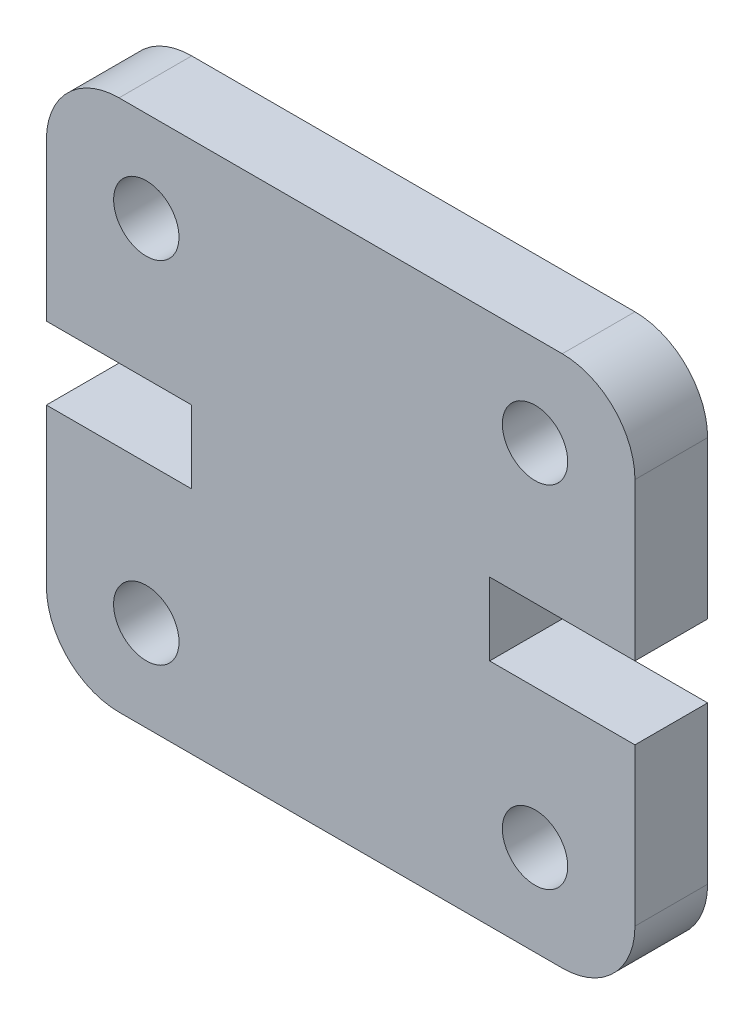
SolidWorks part; units mm, degrees
ref_plane "Front Plane" through (0, 0, 0) normal (0, 0, 1) x (1, 0, 0)
ref_plane "Top Plane" through (0, 0, 0) normal (0, 1, 0) x (1, 0, 0)
ref_plane "Right Plane" through (0, 0, 0) normal (1, 0, 0) x (0, 0, -1)
sketch "Sketch1" plane through (0, 0, 0) normal (0, 0, 1) x (1, 0, 0)
  line L0 (8.1, 14.645) -> (8.1, 0) construction
  line L1 (0, 7.3225) -> (16.2, 7.3225) construction
  line L2 (2, 14.645) -> (14.2, 14.645)
  line L3 (0, 8.3225) -> (4, 8.3225)
  line L4 (0, 8.3225) -> (0, 12.645)
  line L5 (12.2, 6.3225) -> (12.2, 8.3225)
  line L6 (16.2, 6.3225) -> (12.2, 6.3225)
  line L7 (16.2, 6.3225) -> (16.2, 2)
  line L8 (16.2, 8.3225) -> (16.2, 12.645)
  line L9 (16.2, 8.3225) -> (12.2, 8.3225)
  line L12 (0, 6.3225) -> (0, 2)
  line L17 (0, 6.3225) -> (4, 6.3225)
  line L18 (4, 6.3225) -> (4, 8.3225)
  line L19 (2, 0) -> (14.2, 0)
  circle A0 centre (2.75, 12.145) radius 0.9
  arc A1 (0, 12.645) -> (2, 14.645) centre (2, 12.645) cw
  circle A2 centre (13.45, 2.5) radius 0.9
  arc A3 (16.2, 2) -> (14.2, 0) centre (14.2, 2) cw
  arc A4 (16.2, 12.645) -> (14.2, 14.645) centre (14.2, 12.645) ccw
  circle A5 centre (13.45, 12.145) radius 0.9
  arc A11 (0, 2) -> (2, 0) centre (2, 2) ccw
  circle A13 centre (2.75, 2.5) radius 0.9
  point P9 (4, 7.3225)
  point P14 (8.1, 7.3225)
  point P27 (12.2, 7.3225)
  dimension "D2" = 2
  dimension "D8" = 1.8
  dimension "D3" = 2.75
  dimension "D4" = 8.1
  dimension "D5" = 2.5
  dimension "D1" = 1
  dimension "D7" = 4
  dimension "D6" = 6.3225
extrude "Boss-Extrude1" add sketch "Sketch1" along normal blind 4
sketch "Sketch2" plane through (0, 0, 0) normal (0, 0, -1) x (-1, 0, 0)
  line L0 (0, 0) -> (-16.2, 0)
  line L1 (-16.2, 0) -> (-16.2, 14.645)
  line L2 (-16.2, 14.645) -> (0, 14.645)
  line L3 (0, 14.645) -> (0, 0)
extrude "Cut-Extrude1" cut sketch "Sketch2" against normal blind 2
equation "\"D4@Sketch1\"= \"fingerWidth@parametersSketch@prostheticParameters.SLDPRT\" / 2'MIP width"
equation "\"D6@Sketch1\"=( \"HL@parametersSketch@prostheticParameters.SLDPRT\" * 0.117 - 4 - 3 - 2) / 2 'MIP length - Sil. Sht DIP - Sil. Sht MIP"
equation "\"D8@Sketch1\"= 1.5 + \"tol1@parametersSketch@prostheticParameters.SLDPRT\""
